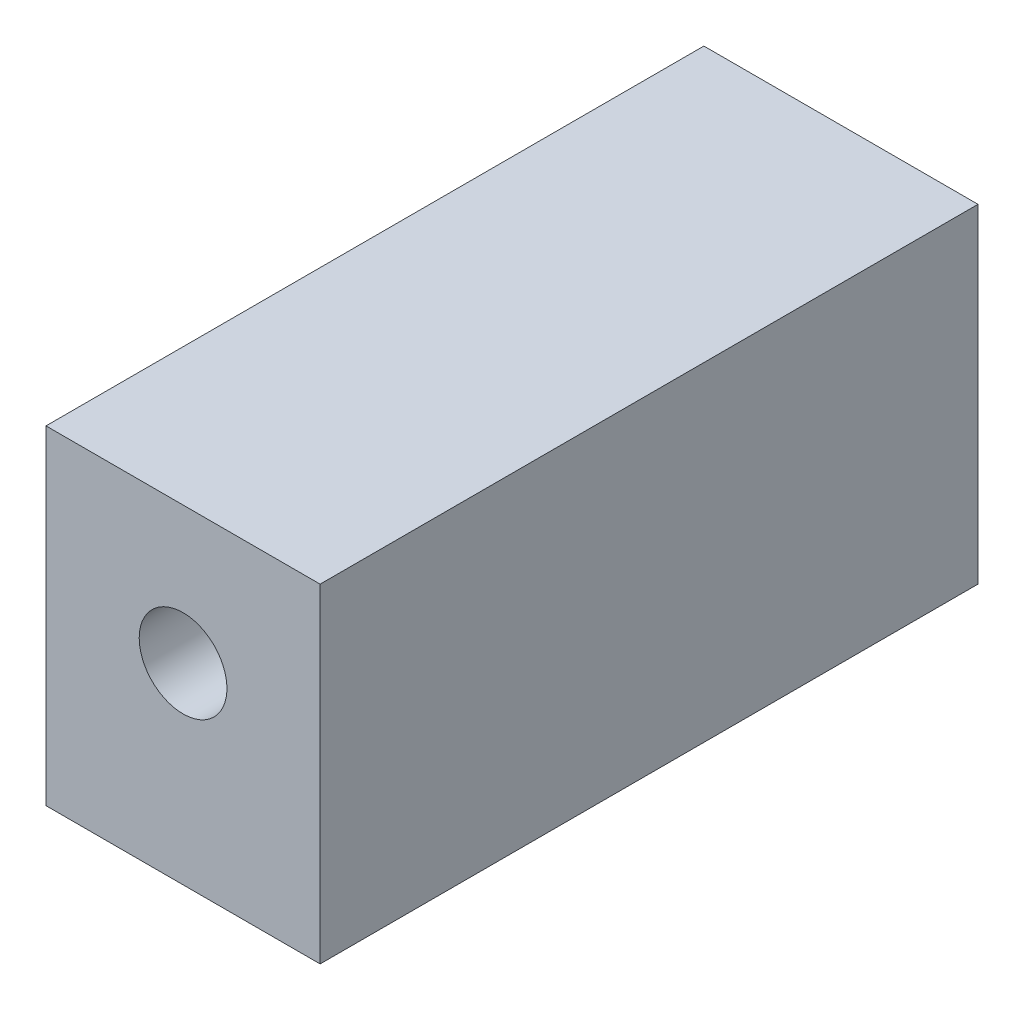
SolidWorks part; units mm, degrees
ref_plane "正面" through (0, 0, 0) normal (0, 0, 1) x (1, 0, 0)
ref_plane "平面" through (0, 0, 0) normal (0, 1, 0) x (1, 0, 0)
ref_plane "右側面" through (0, 0, 0) normal (1, 0, 0) x (0, 0, -1)
sketch "ｽｹｯﾁ1" plane through (0, 0, 0) normal (0, 0, 1) x (1, 0, 0)
  line L1 (-10.5821, 11.8684) -> (14.4179, 11.8684)
  line L2 (-10.5821, 11.8684) -> (-10.5821, -18.1316)
  line L3 (-10.5821, -18.1316) -> (14.4179, -18.1316)
  line L4 (14.4179, 11.8684) -> (14.4179, -18.1316)
  dimension "D1" = 25
  dimension "D2" = 30
extrude "ﾎﾞｽ - 押し出し1" add sketch "ｽｹｯﾁ1" along normal blind 60
sketch "ｽｹｯﾁ2" plane through (0, 0, 0) normal (0, 0, -1) x (-1, 0, 0)
  line L0 (10.5821, 11.8684) -> (10.5821, -18.1316) construction
  line L1 (-14.4179, 11.8684) -> (10.5821, 11.8684) construction
  circle A0 centre (-1.9179, -0.6316) radius 9.8
  dimension "D3" = 19.6
  dimension "D1" = 12.5
  dimension "D2" = 12.5
extrude "ｶｯﾄ - 押し出し1" cut sketch "ｽｹｯﾁ2" against normal blind 50
sketch "ｽｹｯﾁ3" plane through (0, 0, 50) normal (0, 0, -1) x (-1, 0, 0)
  line L0 (10.5821, 11.8684) -> (10.5821, -18.1316) construction
  line L1 (-14.4179, 11.8684) -> (10.5821, 11.8684) construction
  circle A0 centre (-1.9179, -0.6316) radius 4
  dimension "D1" = 8
  dimension "D2" = 12.5
  dimension "D3" = 12.5
extrude "ｶｯﾄ - 押し出し2" cut sketch "ｽｹｯﾁ3" against normal through all
